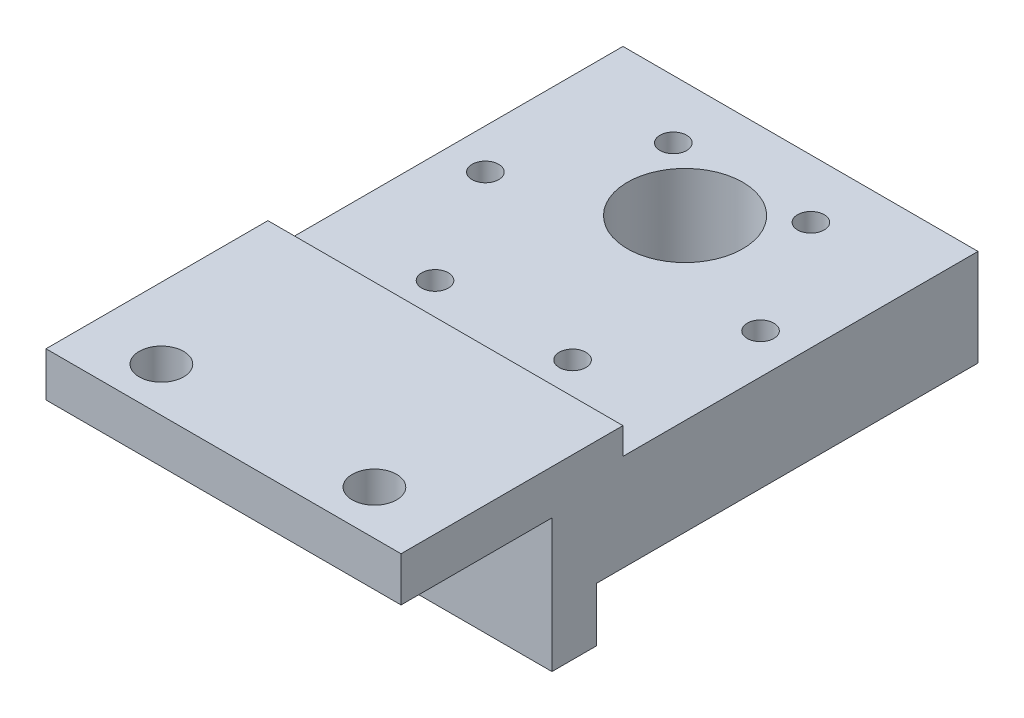
SolidWorks part; units mm, degrees
ref_plane "Front Plane" through (0, 0, 0) normal (0, 0, 1) x (1, 0, 0)
ref_plane "Top Plane" through (0, 0, 0) normal (0, 1, 0) x (1, 0, 0)
ref_plane "Right Plane" through (0, 0, 0) normal (1, 0, 0) x (0, 0, -1)
sketch "Sketch1" plane through (0, 0, 0) normal (0, 1, 0) x (1, 0, 0)
  circle A0 centre (-15.5, 0) radius 1.5
  circle A1 centre (-7.75, 13.4234) radius 1.5
  circle A2 centre (7.75, 13.4234) radius 1.5
  circle A3 centre (15.5, 0) radius 1.5
  circle A4 centre (7.75, -13.4234) radius 1.5
  circle A5 centre (-7.75, -13.4234) radius 1.5
  circle A6 centre (0, 7) radius 6.5
  point P17 (0, 0)
  dimension "D1" = 3
  dimension "D5" = 13
  dimension "D2" = 15.5
  dimension "D3" = 0
  dimension "D6" = 7
  dimension "D4" = 6
sketch "Sketch3" plane through (0, 0, 0) normal (0, 1, 0) x (1, 0, 0)
  line L1 (-20, 20) -> (20, 20)
  line L2 (-20, 20) -> (-20, -45)
  line L3 (-20, -45) -> (20, -45)
  line L4 (20, 20) -> (20, -45)
  dimension "D1" = 65
  dimension "D2" = 40
  dimension "D3" = 20
  dimension "D4" = 20
extrude "Boss-Extrude1" add sketch "Sketch3" along normal blind 5
sketch "Sketch8" plane through (0, 0, 0) normal (0, -1, 0) x (1, 0, 0)
  line L0 (20, 45) -> (20, -20) construction
  line L1 (-20, -20) -> (20, -20)
  line L2 (-20, -20) -> (-20, 23)
  line L3 (-20, 23) -> (20, 23)
  line L4 (20, -20) -> (20, 23)
  dimension "D1" = 43
extrude "Boss-Extrude3" add sketch "Sketch8" along normal blind 8.9
extrude "Cut-Extrude3" cut sketch "Sketch1" along normal through all both and the other way through all
sketch "Sketch6" plane through (0, 5, 0) normal (0, 1, 0) x (1, 0, 0)
  line L0 (-20, 20) -> (-20, -45) construction
  line L1 (-20, -45) -> (20, -45) construction
  circle A0 centre (-12, -40) radius 2.5
  circle A1 centre (12, -40) radius 2.5
  dimension "D1" = 5
  dimension "D4" = 5
  dimension "D2" = 8
  dimension "D3" = 5
  dimension "D5" = 24
  dimension "D9" = 5
extrude "Cut-Extrude6" cut sketch "Sketch6" against normal through all
sketch "Sketch7" plane through (0, 0, 0) normal (0, -1, 0) x (1, 0, 0)
  line L0 (20, 45) -> (20, 23) construction
  line L1 (20, 28) -> (-20, 28)
  line L2 (20, 28) -> (20, 23)
  line L3 (20, 23) -> (-20, 23)
  line L4 (-20, 28) -> (-20, 23)
  line L5 (-20, 23) -> (-20, 45) construction
  line L6 (-20, 45) -> (20, 45) construction
  dimension "D1" = 5
  dimension "D2" = 17
extrude "Boss-Extrude2" add sketch "Sketch7" along normal blind 15
sketch "Sketch9" plane through (-20, 0, 0) normal (-1, 0, 0) x (0, 0, 1)
  line L1 (-20, 5) -> (20, 5)
  line L2 (-20, 5) -> (-20, 2)
  line L3 (-20, 2) -> (20, 2)
  line L4 (20, 5) -> (20, 2)
  dimension "D1" = 40
  dimension "D2" = 3
extrude "Cut-Extrude7" cut sketch "Sketch9" against normal through all
